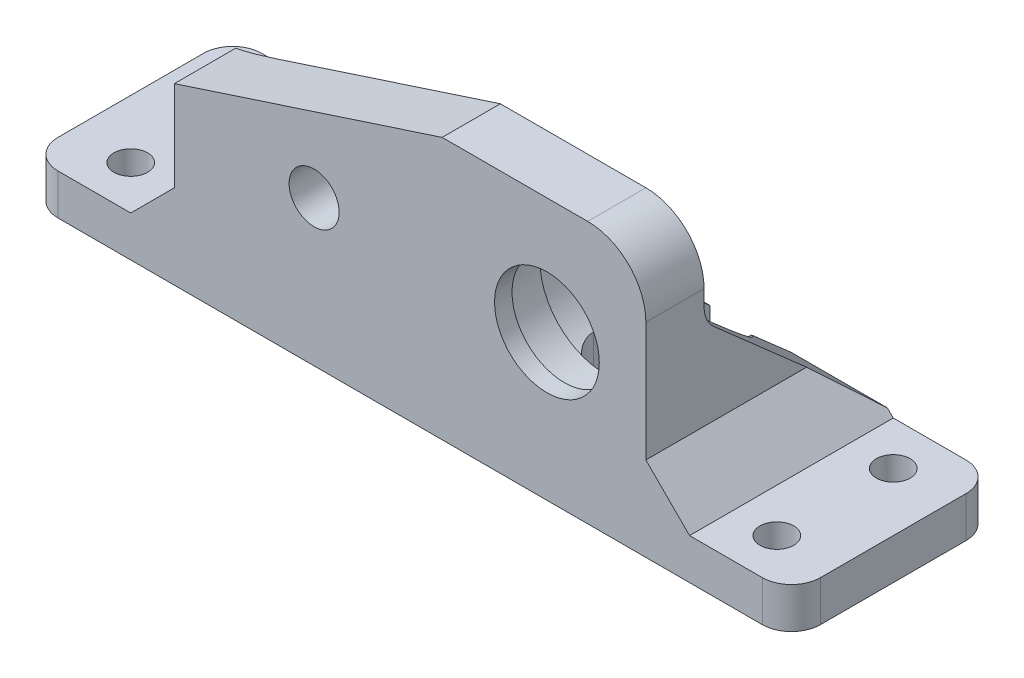
SolidWorks part; units mm, degrees
ref_plane "Front Plane" through (0, 0, 0) normal (0, 0, 1) x (1, 0, 0)
ref_plane "Top Plane" through (0, 0, 0) normal (0, 1, 0) x (1, 0, 0)
ref_plane "Right Plane" through (0, 0, 0) normal (1, 0, 0) x (0, 0, -1)
sketch "Sketch1" plane through (0, 0, 0) normal (0, 0, 1) x (1, 0, 0)
  line L0 (7, 20) -> (-18, 20)
  line L2 (-64, -25) -> (17, -25)
  line L3 (17, 10) -> (17, -25)
  line L4 (-18, 20) -> (-64, 5)
  line L5 (-64, 5) -> (-64, -25)
  circle A0 centre (0, 0) radius 9
  circle A1 centre (-40, 0) radius 4.3
  arc A2 (7, 20) -> (17, 10) centre (7, 10) cw
  dimension "D2" = 18
  dimension "D3" = 8.6
  dimension "D7" = 20
  dimension "D8" = 18
  dimension "D10" = 10
  dimension "D1" = 40
  dimension "D4" = 25
  dimension "D5" = 24
  dimension "D6" = 17
  dimension "D9" = 30
extrude "Boss-Extrude1" add sketch "Sketch1" along normal blind 10
sketch "Sketch3" plane through (-64, 0, 0) normal (-1, 0, 0) x (0, 0, 1)
  line L0 (0, -25) -> (-25, -25)
  line L1 (-25, -25) -> (-25, -17)
  line L2 (-25, -17) -> (0, 5)
  line L3 (0, 5) -> (0, -25)
  dimension "D1" = 25
  dimension "D2" = 8
extrude "Boss-Extrude2" add sketch "Sketch3" against normal blind 10
sketch "Sketch4" plane through (17, 0, 0) normal (1, 0, 0) x (0, 0, -1)
  line L4 (0, 5) -> (0, -25)
  line L5 (0, -25) -> (25, -25)
  line L6 (25, -25) -> (25, -17)
  line L7 (25, -17) -> (0, 5)
  line L8 (0, 5) -> (0, -25)
  line L9 (0, -25) -> (25, -25)
  line L10 (25, -25) -> (25, -17)
  line L11 (25, -17) -> (0, 5)
  dimension "D1" = 0
extrude "Boss-Extrude3" add sketch "Sketch4" against normal blind 10
sketch "Sketch5" plane through (0, 0, 0) normal (1, 0, 0) x (0, 0, -1)
  line L5 (25, -17) -> (0, 5)
  line L6 (25, -25) -> (25, -17)
  line L7 (0, -25) -> (25, -25)
  line L8 (0, -5.6569) -> (0, -25)
  line L9 (0, 5) -> (0, -5.6569)
  line L10 (25, -17) -> (0, 5)
  line L11 (25, -25) -> (25, -17)
  line L12 (0, -25) -> (25, -25)
  line L13 (0, -5.6569) -> (0, -25)
  line L14 (0, 5) -> (0, -5.6569)
  dimension "D1" = 0
extrude "Boss-Extrude4" add sketch "Sketch5" against normal blind 10 from offset 7 offset against normal yes
sketch "Sketch2" plane through (0, 0, 0) normal (0, 0, -1) x (-1, 0, 0)
  circle A0 centre (0, 0) radius 11.2
  dimension "D1" = 22.4
extrude "Cut-Extrude1" cut sketch "Sketch2" against normal blind 7 and the other way through all
fillet "Fillet1" radius 5 7 edges at (-59, 5, 0) (13.511, 5, 0) (7, -16.8715, 0) (-17, -10, 0) (-13.511, 5, 0) (-7, -16.8715, 0)
sketch "Sketch8" plane through (0, 0, -25) normal (0, 0, -1) x (-1, 0, 0)
  circle A0 centre (0, 0) radius 13
  dimension "D1" = 26
extrude "Cut-Extrude4" cut sketch "Sketch8" against normal up to surface (25 mm away) up to face at (-35.7, 0, 0)
sketch "Sketch9" plane through (0, -25, 0) normal (0, -1, 0) x (1, 0, 0)
  line L0 (-64, 10) -> (17, 10) construction
  line L1 (17, -25) -> (42, -25)
  line L2 (17, -25) -> (17, 10)
  line L3 (17, 10) -> (42, 10)
  line L4 (42, -25) -> (42, 10)
  line L5 (-64, -25) -> (-89, -25)
  line L6 (-64, -25) -> (-64, 10)
  line L7 (-64, 10) -> (-89, 10)
  line L8 (-89, -25) -> (-89, 10)
  line L10 (-54, -25) -> (-64, -25) construction
  line L11 (7, -25) -> (17, -25) construction
  line L12 (-17, -25) -> (-7, -25) construction
  line L13 (-17, -25) -> (-54, -25)
  line L14 (-17, -25) -> (-17, 10)
  line L15 (-17, 10) -> (-54, 10)
  line L16 (-54, -25) -> (-54, 10)
  dimension "D1" = 35
  dimension "D2" = 25
extrude "Boss-Extrude5" add sketch "Sketch9" against normal blind 7
fillet "Fillet2" radius 5 4 edges at (42, -21.5, -25) (42, -21.5, 10) (-89, -21.5, 10) (-89, -21.5, -25)
hole_wizard "M5 Clearance Hole1" positions "Sketch11" profile "Sketch10" hole size "M5" standard "ANSI Metric" end condition through all
sketch "Sketch11" plane through (0, -18, 0) normal (0, 1, 0) x (1, 0, 0)
  line L0 (-79, 17.5) -> (32, 17.5) construction
  line L1 (32, 17.5) -> (32, -2.5) construction
  line L2 (32, -2.5) -> (-79, -2.5) construction
  line L3 (-79, -2.5) -> (-79, 17.5) construction
  line L5 (-89, -5) -> (-89, 20) construction
  line L6 (42, 20) -> (42, -5) construction
  line L7 (-84, 25) -> (-64, 25) construction
  line L8 (-64, -10) -> (-84, -10) construction
  point P0 (-79, 17.5)
  point P2 (-79, -2.5)
  point P4 (32, 17.5)
  point P6 (32, -2.5)
  point P33 (-25.5, 17.5)
  dimension "D1" = 20
  dimension "D2" = 10
  dimension "D3" = 10
  dimension "D4" = 7.5
  dimension "D5" = 7.5
  dimension "D6" = 57.5
sketch "Sketch10" plane through (-79, -18, -17.5) normal (1, 0, 0) x (0, 0, 1)
  line L0 (0, 0) -> (0, 7)
  line L1 (0, 7) -> (2.9, 7)
  line L2 (2.9, 7) -> (2.9, 0)
  line L5 (2.9, 0) -> (0, 0)
  line L11 (0, -6.35) -> (0, 107.95) construction
  dimension "Thru Hole Dia." = 5.8
  dimension "Thru Hole Depth" = 7
sketch "Sketch13" plane through (0, 0, -25) normal (0, 0, -1) x (-1, 0, 0)
  line L0 (-17, -18) -> (-24.5, -18)
  line L1 (-17, -18) -> (-37, -18) construction
  line L2 (-24.5, -18) -> (-17, -10.5)
  line L3 (-17, -10.5) -> (-17, -18)
  line L4 (64, -18) -> (71.5, -18)
  line L5 (84, -18) -> (64, -18) construction
  line L6 (71.5, -18) -> (64, -10.5)
  line L7 (64, -10.5) -> (64, -18)
  dimension "D1" = 7.5
  dimension "D2" = 7.5
extrude "Boss-Extrude6" add sketch "Sketch13" against normal up to surface (35 mm away) up to face at (-18.6929, -5.3429, 10)
sketch "Sketch14" plane through (17, 0, 0) normal (-1, 0, 0) x (0, 0, 1)
  line L0 (-25, -17) -> (-25, -10.5)
  line L1 (-25, -10.5) -> (-17.6136, -10.5)
  line L2 (-17.6136, -10.5) -> (-25, -17)
extrude "Cut-Extrude5" cut sketch "Sketch14" against normal through all and the other way through all
